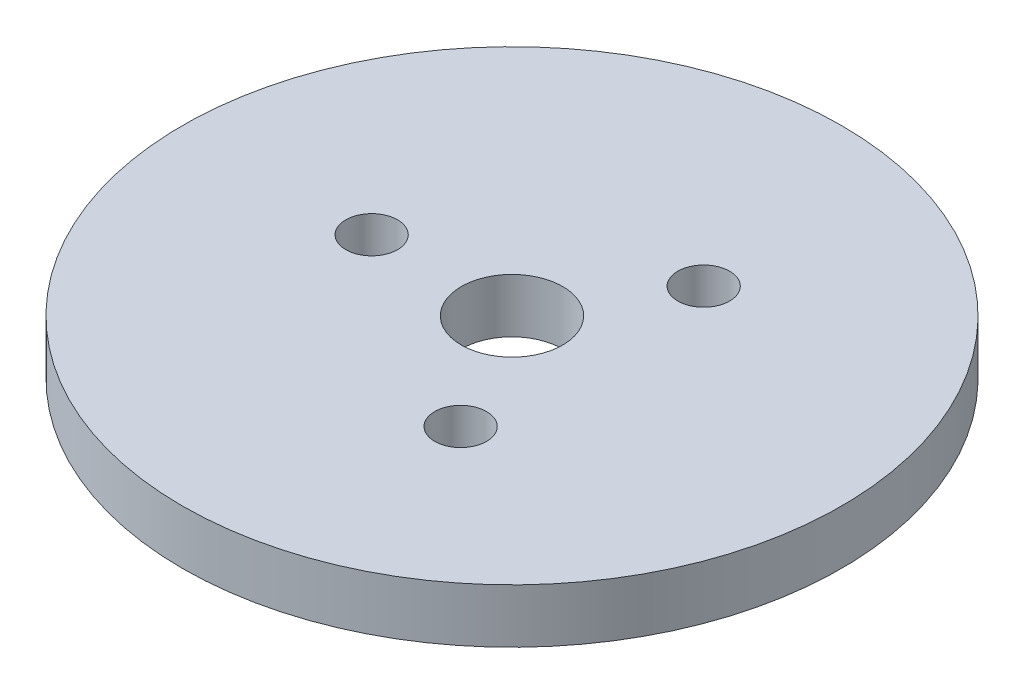
SolidWorks part; units mm, degrees
ref_plane "Front Plane" through (0, 0, 0) normal (0, 0, 1) x (1, 0, 0)
ref_plane "Top Plane" through (0, 0, 0) normal (0, 1, 0) x (1, 0, 0)
ref_plane "Right Plane" through (0, 0, 0) normal (1, 0, 0) x (0, 0, -1)
sketch "Sketch1" plane through (0, 0, 0) normal (0, 1, 0) x (1, 0, 0)
  circle A0 centre (0, 0) radius 97.5
  dimension "FLANGE_OD" = 195
extrude "Boss-Extrude1" add sketch "Sketch1" along normal blind 16
sketch "Sketch2" plane through (0, 0, 0) normal (0, 1, 0) x (1, 0, 0)
  circle A0 centre (0, 0) radius 15
  dimension "BORE_D" = 30
extrude "Cut-Extrude1" cut sketch "Sketch2" along normal through all
sketch "Sketch3" plane through (0, 16, 0) normal (0, 1, 0) x (1, 0, 0)
  circle A0 centre (0, 0) radius 41.5207 construction
  circle A1 centre (-41.5207, 0) radius 7.6633
  dimension "BOLT_D" = 15.3266
  dimension "BOLT_PCD" = 83.0414
extrude "Cut-Extrude2" cut sketch "Sketch3" against normal blind 11.332
pattern_circular "CirPattern1" count 3 over 360 about axis through (0, 0, 0) along (0, 1, 0) of "Cut-Extrude2"
